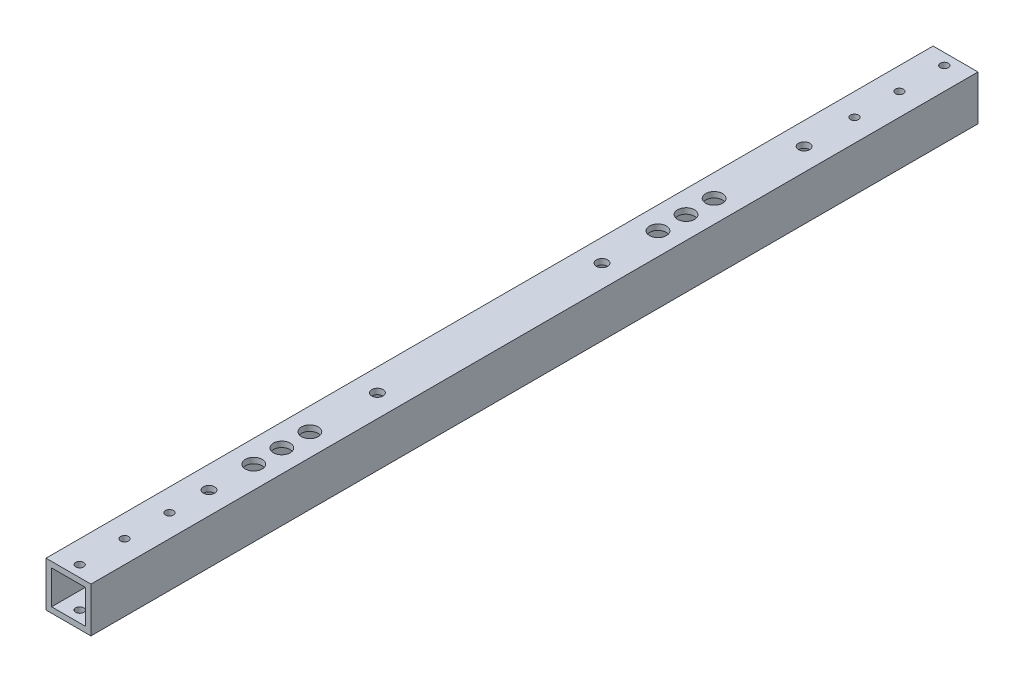
SolidWorks part; units mm, degrees
material "6061-T6 (SS)"
ref_plane "Front Plane" through (0, 0, 0) normal (0, 0, 1) x (1, 0, 0)
ref_plane "Top Plane" through (0, 0, 0) normal (0, 1, 0) x (1, 0, 0)
ref_plane "Right Plane" through (0, 0, 0) normal (1, 0, 0) x (0, 0, -1)
sketch "Sketch1" plane through (0, 0, 0) normal (0, 0, 1) x (1, 0, 0)
  line L1 (-12.7, -12.7) -> (12.7, -12.7)
  line L2 (-12.7, -12.7) -> (-12.7, 12.7)
  line L3 (-12.7, 12.7) -> (12.7, 12.7)
  line L4 (12.7, -12.7) -> (12.7, 12.7)
  line L5 (-12.7, -12.7) -> (12.7, 12.7) construction
  line L6 (-12.7, 12.7) -> (12.7, -12.7) construction
  point P0 (0, 0)
  dimension "D1" = 25.4
  dimension "D2" = 25.4
extrude "Extrude-Thin1" add sketch "Sketch1" along normal blind 501.65 thin thin type one direction reverse wall 3.175
hole_wizard "#8 Clearance Hole1" positions "3DSketch1" profile "Sketch3" hole size "#8" standard "ANSI Inch" end condition through all
sketch3d "3DSketch1"
  line L1 (12.7, 12.7, 0) -> (-12.7, 12.7, 0) construction
  line L6 (0, 12.7, 501.65) -> (0, 12.7, 0) construction
  line L7 (12.7, 12.7, 501.65) -> (-12.7, 12.7, 501.65) construction
  point P57 (0, 12.7, 6.35)
  point P59 (0, 12.7, 31.75)
  point P61 (0, 12.7, 57.15)
  point P63 (0, 12.7, 469.9)
  point P65 (0, 12.7, 444.5)
  point P67 (0, 12.7, 495.3)
  dimension "D1" = 25.4
  dimension "D2" = 25.4
  dimension "D3" = 6.35
  dimension "D4" = 25.4
  dimension "D5" = 25.4
  dimension "D6" = 6.35
sketch "Sketch3" plane through (0, 12.7, 495.3) normal (1, 0, 0) x (0, 0, 1)
  line L0 (0, 0) -> (0, 25.4)
  line L1 (0, 25.4) -> (2.2479, 25.4)
  line L2 (2.2479, 25.4) -> (2.2479, 0)
  line L5 (2.2479, 0) -> (0, 0)
  line L11 (0, -6.35) -> (0, 107.95) construction
  dimension "Thru Hole Dia." = 4.4958
  dimension "Thru Hole Depth" = 25.4
hole_wizard "1/4 (0.25) Diameter Hole1" positions "Sketch6" profile "Sketch7" hole size "1/4" standard "ANSI Inch"
sketch "Sketch6" plane through (0, 12.7, 0) normal (0, 1, 0) x (1, 0, 0)
  point P0 (0, -199.9335)
  point P15 (0, -422.2)
  point P23 (0, -326.95)
  point P26 (0, -85.6235)
sketch "Sketch7" plane through (0, 12.7, 199.9335) normal (1, 0, 0) x (0, 0, 1)
  line L0 (0, 0) -> (0, 27.3077)
  line L1 (0, 27.3077) -> (3.175, 25.4)
  line L2 (3.175, 25.4) -> (3.175, 0)
  line L5 (3.175, 0) -> (0, 0)
  line L10 (0, 27.3077) -> (-3.175, 25.4) construction
  line L11 (0, -6.35) -> (0, 107.95) construction
  dimension "Hole Dia." = 6.35
  dimension "Hole Depth" = 25.4
  dimension "Drill Angle" = 118
hole_wizard "" positions "Sketch17" profile "Sketch18" hole size "3/8" standard "ANSI Inch" end condition through all
sketch "Sketch17" plane through (-381, 12.7, 250.825) normal (0, 1, 0) x (1, 0, 0)
  point P0 (381, 82.55)
  point P3 (381, 98.425)
  point P6 (381, 114.3)
  point P9 (381, -146.05)
  point P12 (381, -130.175)
  point P15 (381, -114.3)
  point P18 (-381, -146.05)
  point P21 (-381, -130.175)
  point P24 (-381, -114.3)
  point P27 (-381, 82.55)
  point P30 (-381, 98.425)
  point P33 (-381, 114.3)
  point P36 (-92.583, 346.075)
  point P39 (-35.433, 346.075)
  point P42 (92.964, 346.075)
  point P45 (35.814, 346.075)
  point P48 (-22.9616, -346.775)
  point P51 (50.0634, -346.775)
  point P54 (123.0884, -346.775)
sketch "Sketch18" plane through (0, 12.7, 168.275) normal (1, 0, 0) x (0, 0, 1)
  line L0 (0, 0) -> (0, 25.4)
  line L1 (0, 25.4) -> (4.7625, 25.4)
  line L2 (4.7625, 25.4) -> (4.7625, 0)
  line L3 (4.7625, 0) -> (0, 0)
  line L4 (0, -6.35) -> (0, 107.95) construction
  dimension "Thru Hole Dia." = 9.525
  dimension "Thru Hole Depth" = 25.4
